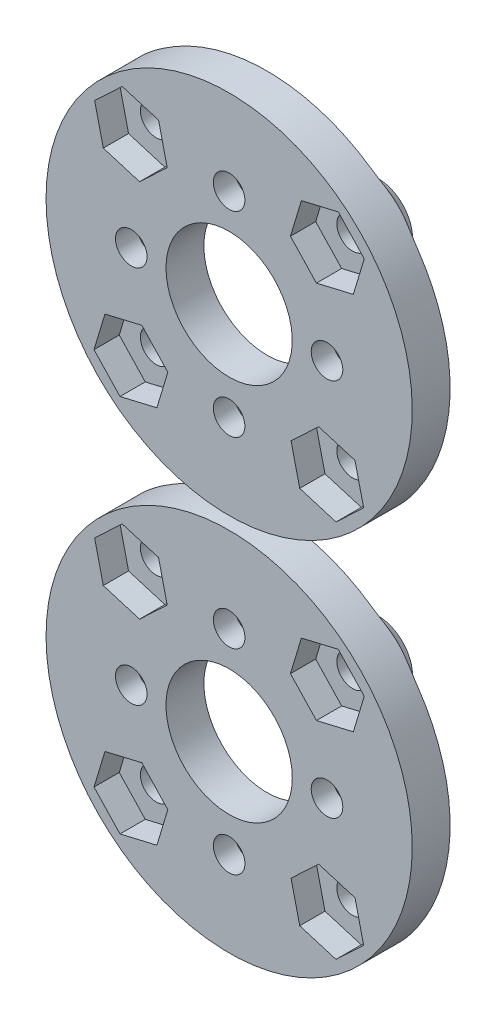
SolidWorks part; units mm, degrees
note: The reader was unsure of these and kept them because the rebuilt part matched: shared geometry of "草图1<6>".
ref_plane "前视基准面" through (0, 0, 0) normal (0, 0, 1) x (1, 0, 0)
ref_plane "上视基准面" through (0, 0, 0) normal (0, 1, 0) x (1, 0, 0)
ref_plane "右视基准面" through (0, 0, 0) normal (1, 0, 0) x (0, 0, -1)
sketch "草图1" plane through (0, 0, 0) normal (0, 0, 1) x (1, 0, 0)
  circle A0 centre (0, 0) radius 7.75 construction
  circle A1 centre (0, 7.75) radius 1.25
  circle A2 centre (7.75, 0) radius 1.25
  circle A3 centre (0, -7.75) radius 1.25
  circle A4 centre (-7.75, 0) radius 1.25
  circle A5 centre (0, 7.75) radius 2.3
  circle A6 centre (7.75, 0) radius 2.3
  circle A7 centre (0, -7.75) radius 2.3
  circle A8 centre (-7.75, 0) radius 2.3
  circle A9 centre (0, 0) radius 14.5
  circle A10 centre (0, 0) radius 5
  dimension "D2" = 2.5
  dimension "D3" = 15.5
  dimension "D4" = 4.6
  dimension "D5" = 4
  dimension "D6" = 29
  dimension "D7" = 10
  dimension "D1" = 4
extrude "凸台-拉伸5" add sketch "草图1" along normal blind 3 contours A9 A10 A6 A7 A8 A5 | A10 A8 A4 | A10 A5 A1 | A10 A6 A2 | A10 A7 A3
extrude "切除-拉伸1" cut sketch "草图1<6>" along normal blind 1.3 contours A10 A6 A2 | A10 A5 A1 | A10 A8 A4 | A10 A7 A3
sketch "草图1<6>" plane through (0, 0, 0) normal (0, 0, 1) x (1, 0, 0) same geometry as "草图1"
sketch "草图2" plane through (0, 0, 0) normal (0, 0, 1) x (1, 0, 0)
  line L0 (0, 0) -> (-7.7782, 7.7782) construction
  circle A0 centre (0, 0) radius 11 construction
  circle A1 centre (-7.7782, 7.7782) radius 1.25
  circle A2 centre (7.7782, 7.7782) radius 1.25
  circle A3 centre (7.7782, -7.7782) radius 1.25
  circle A4 centre (-7.7782, -7.7782) radius 1.25
  dimension "D1" = 22
  dimension "D2" = 2.5
  dimension "D3" = 4
extrude "切除-拉伸2" cut sketch "草图2" along normal blind 31
ref_plane "基准面1" through (0, 0, 0) normal (0, 0, -1) x (-1, 0, 0)
sketch "草图3" plane through (0, 0, 0) normal (0, 0, -1) x (-1, 0, 0)
  circle A0 centre (7.7782, 7.7782) radius 2.75
  circle A1 centre (7.7782, -7.7782) radius 2.75
  circle A2 centre (-7.7782, -7.7782) radius 2.75
  circle A3 centre (-7.7782, 7.7782) radius 2.75
  circle A4 centre (7.7782, 7.7782) radius 1.25
  circle A5 centre (7.7782, -7.7782) radius 1.25
  circle A6 centre (-7.7782, -7.7782) radius 1.25
  circle A7 centre (-7.7782, 7.7782) radius 1.25
  dimension "D3" = 1.5
  dimension "D1" = 4
  dimension "D2" = 4
extrude "凸台-拉伸6" add sketch "草图3" along normal blind 1
fillet "圆角1" radius 1.5 4 edges at (10.5282, -7.7782, 0) (-5.0282, -7.7782, 0) (-5.0282, 7.7782, 0) (10.5282, 7.7782, 0)
ref_plane "基准面2" through (0, 0, 3) normal (0, 0, 1) x (1, 0, 0)
sketch "草图4" plane through (0, 0, 3) normal (0, 0, 1) x (1, 0, 0)
  line L0 (6.9114, 4.9038) -> (9.8341, 5.5903)
  line L1 (-8.4647, 10.7008) -> (-10.6525, 8.645)
  line L2 (-10.6525, 8.645) -> (-9.966, 5.7223)
  line L3 (-9.966, 5.7223) -> (-7.0917, 4.8555)
  line L4 (-7.0917, 4.8555) -> (-4.9038, 6.9114)
  line L5 (-4.9038, 6.9114) -> (-5.5903, 9.8341)
  line L6 (-5.5903, 9.8341) -> (-8.4647, 10.7008)
  line L7 (9.8341, 5.5903) -> (10.7008, 8.4647)
  line L8 (8.645, 10.6525) -> (5.7223, 9.966)
  line L9 (10.7008, 8.4647) -> (8.645, 10.6525)
  line L10 (5.7223, 9.966) -> (4.8555, 7.0917)
  line L11 (4.8555, 7.0917) -> (6.9114, 4.9038)
  line L12 (4.9038, -6.9114) -> (5.5903, -9.8341)
  line L13 (5.5903, -9.8341) -> (8.4647, -10.7008)
  line L14 (10.6525, -8.645) -> (9.966, -5.7223)
  line L15 (8.4647, -10.7008) -> (10.6525, -8.645)
  line L16 (9.966, -5.7223) -> (7.0917, -4.8555)
  line L17 (7.0917, -4.8555) -> (4.9038, -6.9114)
  line L18 (-6.9114, -4.9038) -> (-9.8341, -5.5903)
  line L19 (-9.8341, -5.5903) -> (-10.7008, -8.4647)
  line L20 (-8.645, -10.6525) -> (-5.7223, -9.966)
  line L21 (-10.7008, -8.4647) -> (-8.645, -10.6525)
  line L22 (-5.7223, -9.966) -> (-4.8555, -7.0917)
  line L23 (-4.8555, -7.0917) -> (-6.9114, -4.9038)
  circle A0 centre (-7.7782, 7.7782) radius 2.6 construction
  dimension "D1" = 5.2
  dimension "D2" = 4
extrude "切除-拉伸3" cut sketch "草图4" against normal blind 2
sketch "草图5" plane through (0, 0, 0) normal (0, 0, 1) x (1, 0, 0)
  circle A0 centre (0, 15) radius 15
  dimension "D1" = 30
sketch "草图6" plane through (0, 0, 0) normal (1, 0, 0) x (0, 0, -1)
  line L0 (0, 15) -> (-18.6025, 15)
  line L1 (0, 30) -> (0, 0) construction
pattern_circular "阵列(圆周)2" count 2 every 180 about axis through (0, 15, 0) along (0, 0, 1) of bodies 110
sketch "草图7" plane through (0, 0, 0) normal (0, 0, 1) x (1, 0, 0)
  line L1 (-0.5, 15.9785) -> (0.5, 15.9785)
  line L2 (-0.5, 15.9785) -> (-0.5, 14.0215)
  line L3 (-0.5, 14.0215) -> (0.5, 14.0215)
  line L4 (0.5, 15.9785) -> (0.5, 14.0215)
  line L5 (-0.5, 15.9785) -> (0.5, 14.0215) construction
  line L6 (-0.5, 14.0215) -> (0.5, 15.9785) construction
  point P0 (0, 15)
  dimension "D1" = 1
extrude "凸台-拉伸7" add sketch "草图7" along normal blind 1
